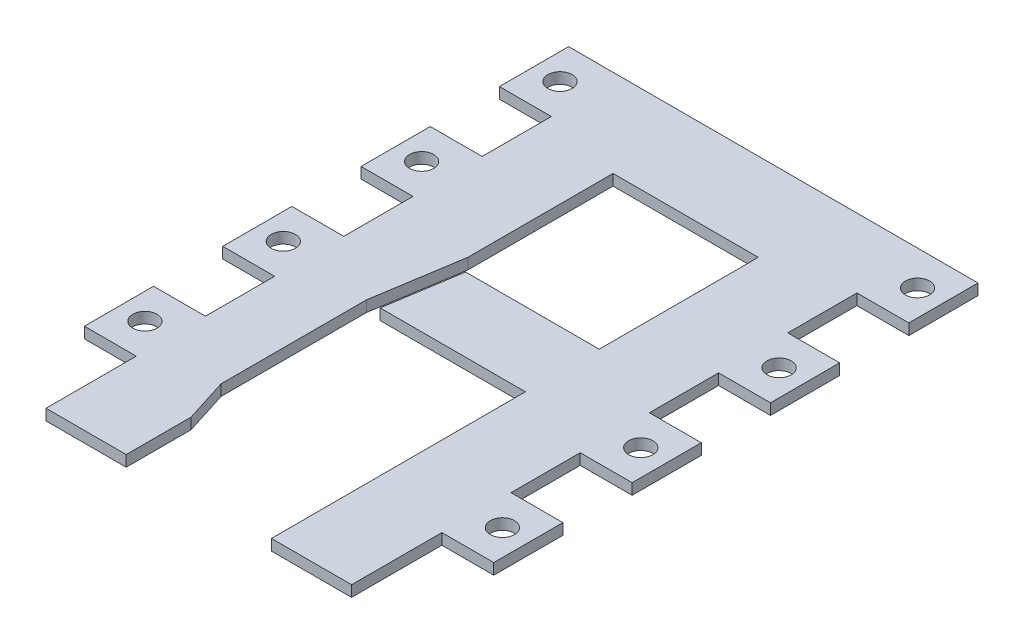
SolidWorks part; units mm, degrees
ref_plane "Front Plane" through (0, 0, 0) normal (0, 0, 1) x (1, 0, 0)
ref_plane "Top Plane" through (0, 0, 0) normal (0, 1, 0) x (1, 0, 0)
ref_plane "Right Plane" through (0, 0, 0) normal (1, 0, 0) x (0, 0, -1)
sketch "Sketch1" plane through (0, 0, 0) normal (0, 1, 0) x (1, 0, 0)
  line L0 (44.175, 25.3333) -> (44.175, 0) construction
  line L1 (0, 0) -> (88.35, 0)
  line L2 (0, 0) -> (0, 160)
  line L3 (0, 160) -> (88.35, 160)
  line L4 (88.35, 0) -> (88.35, 160)
  line L5 (23.175, 134.6667) -> (65.175, 134.6667)
  line L6 (23.175, 134.6667) -> (23.175, 92.6667)
  line L7 (23.175, 92.6667) -> (65.175, 92.6667)
  line L8 (65.175, 134.6667) -> (65.175, 92.6667)
  line L9 (23.175, 67.3333) -> (65.175, 67.3333)
  line L10 (23.175, 67.3333) -> (23.175, 25.3333)
  line L11 (23.175, 25.3333) -> (65.175, 25.3333)
  line L12 (65.175, 67.3333) -> (65.175, 25.3333)
  line L13 (44.175, 134.6667) -> (44.175, 160) construction
  line L14 (44.175, 67.3333) -> (44.175, 92.6667) construction
  line L15 (23.175, 92.6667) -> (19.175, 67.3333)
  line L16 (23.175, 25.3333) -> (27.175, 25.3333)
  line L17 (23.175, 25.3333) -> (23.175, 0)
  line L18 (23.175, 0) -> (27.175, 0)
  line L19 (27.175, 25.3333) -> (27.175, 0)
  line L20 (65.175, 25.3333) -> (61.175, 25.3333)
  line L21 (65.175, 25.3333) -> (65.175, 0)
  line L22 (65.175, 0) -> (61.175, 0)
  line L23 (61.175, 25.3333) -> (61.175, 0)
  line L24 (19.175, 67.3333) -> (19.175, 25.3333)
  line L25 (19.175, 25.3333) -> (23.175, 12.6667)
  line L26 (27.175, 92.6667) -> (23.175, 67.3333)
  line L27 (19.175, 67.3333) -> (23.175, 67.3333) construction
  line L28 (27.175, 92.6667) -> (23.175, 92.6667)
  line L29 (23.175, 12.6667) -> (23.175, 25.3333)
  line L30 (65.175, 92.6667) -> (65.175, 88.6667)
  line L31 (65.175, 88.6667) -> (26.5434, 88.6667)
  point P13 (44.175, 67.3333)
  point P14 (44.175, 92.6667)
  point P15 (44.175, 134.6667)
  point P16 (44.175, 160)
  dimension "D1" = 88.35
  dimension "D2" = 160
  dimension "D3" = 42
  dimension "D4" = 4
extrude "Boss-Extrude1" add sketch "Sketch1" along normal blind 3.175 contours L30 L31 L26 L9 L12 L21 L1 L4 L3 L2 L17 L25 L24 L15 L6 L5 L8 region at (44.8649, 0, -88.4824)
sketch "Sketch3" plane through (0, 3.175, 0) normal (0, 1, 0) x (1, 0, 0)
  line L0 (0, 0) -> (0, 160) construction
  line L1 (0, 160) -> (-15, 160)
  line L2 (0, 160) -> (0, 140)
  line L3 (0, 140) -> (-15, 140)
  line L4 (-15, 160) -> (-15, 140)
  line L5 (0, 120) -> (0, 100)
  line L6 (0, 120) -> (-15, 120)
  line L7 (-15, 120) -> (-15, 100)
  line L8 (0, 100) -> (-15, 100)
  line L9 (0, 80) -> (0, 60)
  line L10 (0, 80) -> (-15, 80)
  line L11 (-15, 80) -> (-15, 60)
  line L12 (0, 60) -> (-15, 60)
  line L13 (0, 40) -> (0, 20)
  line L14 (0, 40) -> (-15, 40)
  line L15 (-15, 40) -> (-15, 20)
  line L16 (0, 20) -> (-15, 20)
  line L17 (-15, 20) -> (-15, 0) construction
  line L18 (0, 0) -> (23.175, 0) construction
  line L19 (44.175, 160) -> (44.175, 134.6667) construction
  line L20 (0, 160) -> (88.35, 160) construction
  line L21 (23.175, 134.6667) -> (65.175, 134.6667) construction
  line L22 (103.35, 20) -> (103.35, 0) construction
  line L23 (88.35, 20) -> (103.35, 20)
  line L24 (103.35, 40) -> (103.35, 20)
  line L25 (88.35, 40) -> (103.35, 40)
  line L26 (88.35, 40) -> (88.35, 20)
  line L27 (88.35, 60) -> (103.35, 60)
  line L28 (103.35, 80) -> (103.35, 60)
  line L29 (88.35, 80) -> (103.35, 80)
  line L30 (88.35, 80) -> (88.35, 60)
  line L31 (88.35, 100) -> (103.35, 100)
  line L32 (103.35, 120) -> (103.35, 100)
  line L33 (88.35, 120) -> (103.35, 120)
  line L34 (88.35, 120) -> (88.35, 100)
  line L35 (103.35, 160) -> (103.35, 140)
  line L36 (88.35, 140) -> (103.35, 140)
  line L37 (88.35, 160) -> (88.35, 140)
  line L38 (88.35, 160) -> (103.35, 160)
  circle A0 centre (-7.5, 150) radius 3.5
  circle A1 centre (-7.5, 110) radius 3.5
  circle A2 centre (-7.5, 70) radius 3.5
  circle A3 centre (-7.5, 30) radius 3.5
  circle A4 centre (95.85, 30) radius 3.5
  circle A5 centre (95.85, 70) radius 3.5
  circle A6 centre (95.85, 110) radius 3.5
  circle A7 centre (95.85, 150) radius 3.5
  point P6 (-7.5, 160)
  point P12 (-15, 150)
  dimension "D3" = 7
  dimension "D1" = 20
  dimension "D2" = 15
  dimension "D4" = 4
extrude "Boss-Extrude3" add sketch "Sketch3" against normal up to surface (3.175 mm away) up to face at (38.6355, 0, -68.7083)
sketch "Sketch4" plane through (0, 3.175, 0) normal (0, 1, 0) x (1, 0, 0)
  line L1 (23.175, 0) -> (0, 0)
  line L2 (23.175, 0) -> (23.175, -6.096)
  line L3 (23.175, -6.096) -> (0, -6.096)
  line L4 (0, 0) -> (0, -6.096)
  line L5 (65.175, 0) -> (88.35, 0)
  line L6 (65.175, 0) -> (65.175, -6.096)
  line L7 (65.175, -6.096) -> (88.35, -6.096)
  line L8 (88.35, 0) -> (88.35, -6.096)
  point P10 (88.35, -23.175)
  point P11 (23.175, -45.8967)
  point P12 (81.9769, -15.3131)
  point P13 (88.35, 0)
  point P15 (23.175, -8.3757)
  dimension "D1" = 88.35
  dimension "D2" = 6.096
extrude "Boss-Extrude4" add sketch "Sketch4" against normal up to surface (3.175 mm away) up to face at (42.1606, 0, -75.8939)
